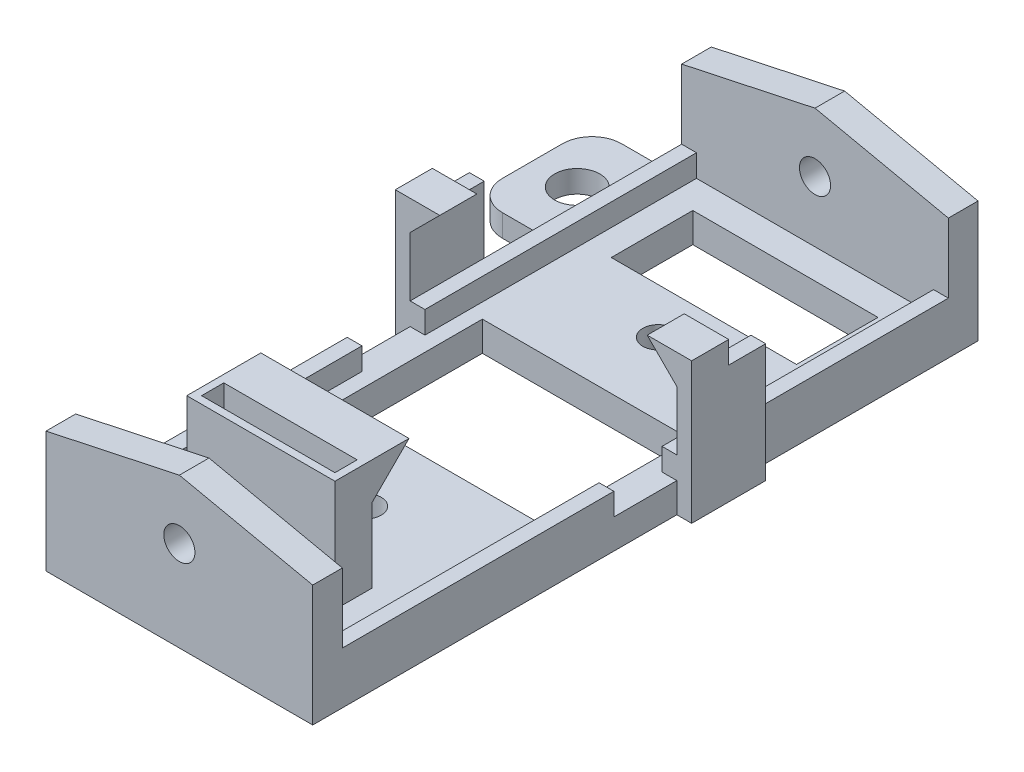
SolidWorks part; units mm, degrees
ref_plane "Front Plane" through (0, 0, 0) normal (0, 0, 1) x (1, 0, 0)
ref_plane "Top Plane" through (0, 0, 0) normal (0, 1, 0) x (1, 0, 0)
ref_plane "Right Plane" through (0, 0, 0) normal (1, 0, 0) x (0, 0, -1)
sketch "Sketch1" plane through (0, 0, 0) normal (0, 0, 1) x (1, 0, 0)
  line L2 (-40.4, 110) -> (0, 118.6383) construction
  line L3 (-18, 114.7896) -> (0, 114.7896)
  line L4 (0, 114.7896) -> (18, 114.7896)
  line L5 (0, 118.6383) -> (40.4, 110) construction
  line L11 (18, 114.7896) -> (18, 121.7896)
  line L12 (18, 121.7896) -> (16, 121.7896)
  line L13 (16, 121.7896) -> (16, 118.7896)
  line L14 (16, 118.7896) -> (-16, 118.7896)
  line L15 (-16, 118.7896) -> (-16, 121.7896)
  line L16 (-16, 121.7896) -> (-18, 121.7896)
  line L17 (-18, 121.7896) -> (-18, 114.7896)
  point P15 (0, 118.7896)
  dimension "D1" = 32
  dimension "D2" = 2
  dimension "D3" = 3
  dimension "D4" = 4
extrude "Boss-Extrude1" add sketch "Sketch1" along normal up to surface (89.8 mm away)
sketch "Sketch2" plane through (0, 114.7896, 0) normal (0, -1, 0) x (1, 0, 0)
  line L0 (18, 89.8) -> (18, 0) construction
  line L5 (-14, 54.9) -> (14, 54.9)
  line L6 (-14, 54.9) -> (-14, 34.9)
  line L7 (-14, 34.9) -> (14, 34.9)
  line L8 (14, 54.9) -> (14, 34.9)
  point P4 (0, 34.9)
  point P8 (18, 44.9)
  point P9 (14, 44.9)
  dimension "D1" = 4
  dimension "D2" = 20
extrude "Cut-Extrude1" cut sketch "Sketch2" against normal up to next
sketch "Sketch3" plane through (-18, 0, 0) normal (-1, 0, 0) x (0, 0, 1)
  line L0 (89.8, 121.7896) -> (0, 121.7896) construction
  line L1 (40.65, 118.7896) -> (49.15, 118.7896)
  line L2 (40.65, 118.7896) -> (40.65, 121.7896)
  line L3 (40.65, 121.7896) -> (49.15, 121.7896)
  line L4 (49.15, 118.7896) -> (49.15, 121.7896)
  line L5 (89.8, 118.7896) -> (0, 118.7896) construction
  point P9 (44.9, 121.7896)
  point P10 (44.9, 121.7896)
  dimension "D1" = 8.5
extrude "Cut-Extrude2" cut sketch "Sketch3" against normal through all
sketch "Sketch4" plane through (0, 118.7896, 0) normal (0, 1, 0) x (1, 0, 0)
  circle A0 centre (0, -25.15) radius 2.1 construction
  circle A1 centre (0, -64.65) radius 2.1 construction
  circle A2 centre (0, -25.15) radius 2.1
  circle A3 centre (0, -64.65) radius 2.1
extrude "Cut-Extrude3" cut sketch "Sketch4" against normal through all
ref_plane "Plane2" through (0, 0, 44.9) normal (0, 0, -1) x (-1, 0, 0)
sketch "Sketch5" plane through (0, 0, 0) normal (0, 0, 1) x (1, 0, 0)
  line L0 (-18, 114.7896) -> (-18, 131.1512)
  line L1 (-56.4, 122.9405) -> (0, 135) construction
  line L2 (-18, 131.1512) -> (0, 135)
  line L3 (0, 135) -> (18, 131.1512)
  line L4 (0, 135) -> (56.4, 122.9405) construction
  line L5 (18, 131.1512) -> (18, 114.7896)
  line L6 (18, 114.7896) -> (-18, 114.7896)
  line L7 (0.6273, 134.8659) -> (54.0273, 123.4479) construction
  line L8 (-54.0273, 123.4479) -> (-0.6273, 134.8659) construction
  circle A0 centre (0, 127) radius 2.1
  dimension "D1" = 4.2
  dimension "D2" = 8
extrude "Boss-Extrude2" add sketch "Sketch5" along normal blind 4
mirror "Mirror1" about plane through (0, 0, 44.9) normal (0, 0, -1) of "Boss-Extrude2"
sketch "Sketch6" plane through (0, 118.7896, 0) normal (0, 1, 0) x (1, 0, 0)
  line L1 (12.5, -19) -> (-12.5, -19)
  line L2 (12.5, -19) -> (12.5, -8)
  line L3 (12.5, -8) -> (-12.5, -8)
  line L4 (-12.5, -19) -> (-12.5, -8)
  point P4 (0, -8)
  dimension "D1" = 11
  dimension "D2" = 25
  dimension "D3" = 8
extrude "Cut-Extrude4" cut sketch "Sketch6" against normal through all
sketch "Sketch8" plane through (0, 118.7896, 0) normal (0, 1, 0) x (1, 0, 0)
  line L0 (16, -85.8) -> (-16, -85.8) construction
  line L1 (9, -77.8) -> (-9, -77.8)
  line L2 (9, -77.8) -> (9, -74.8)
  line L3 (9, -74.8) -> (-9, -74.8)
  line L4 (-9, -77.8) -> (-9, -74.8)
  line L6 (10, -73.8) -> (-10, -73.8)
  line L7 (-10, -78.8) -> (-10, -73.8)
  line L8 (10, -78.8) -> (-10, -78.8)
  line L9 (10, -78.8) -> (10, -73.8)
  point P6 (0, -85.8)
  point P7 (0, -77.8)
  dimension "D1" = 8
  dimension "D2" = 3
  dimension "D3" = 18
  dimension "D4" = 1
extrude "Boss-Extrude3" add sketch "Sketch8" along normal blind 15
sketch "Sketch9" plane through (-10, 0, 0) normal (-1, 0, 0) x (0, 0, 1)
  line L0 (73.8, 128.7896) -> (68.8, 133.7896)
  line L1 (73.8, 133.7896) -> (73.8, 118.7896) construction
  line L2 (68.8, 133.7896) -> (73.8, 133.7896)
  line L3 (73.8, 133.7896) -> (73.8, 128.7896)
  dimension "D1" = 5
  dimension "D2" = 45
extrude "Boss-Extrude4" add sketch "Sketch9" against normal up to surface (20 mm away) up to face at (10, 126.2896, 76.3)
sketch "Sketch13" plane through (0, 118.7896, 0) normal (0, 1, 0) x (1, 0, 0)
  line L4 (-9, -77.8) -> (9, -77.8)
  line L5 (9, -77.8) -> (9, -74.8)
  line L6 (9, -74.8) -> (-9, -74.8)
  line L7 (-9, -74.8) -> (-9, -77.8)
  line L8 (-9, -77.8) -> (9, -77.8)
  line L9 (9, -77.8) -> (9, -74.8)
  line L10 (9, -74.8) -> (-9, -74.8)
  line L11 (-9, -74.8) -> (-9, -77.8)
  dimension "D1" = 0
extrude "Cut-Extrude5" cut sketch "Sketch13" against normal through all
sketch "Sketch10" plane through (0, 114.7896, 0) normal (0, 1, 0) x (1, 0, 0)
  line L0 (18, -40.65) -> (18, -4) construction
  line L1 (18, -40.65) -> (20, -40.65)
  line L2 (18, -40.65) -> (18, -30.65)
  line L3 (18, -30.65) -> (20, -30.65)
  line L4 (20, -40.65) -> (20, -30.65)
  line L5 (0, -1000) -> (0, 49000) construction
  line L6 (-18, -30.65) -> (-20, -30.65)
  line L7 (-18, -40.65) -> (-18, -30.65)
  line L8 (-18, -40.65) -> (-20, -40.65)
  line L9 (-20, -40.65) -> (-20, -30.65)
  dimension "D1" = 10
  dimension "D2" = 2
extrude "Boss-Extrude5" add sketch "Sketch10" along normal offset from surface (16 mm away) 3
sketch "Sketch12" plane through (0, 0, 40.65) normal (0, 0, 1) x (1, 0, 0)
  line L0 (20, 129.7896) -> (20, 133.7896)
  line L1 (20, 133.7896) -> (14, 133.7896)
  line L2 (14, 133.7896) -> (18, 129.7896)
  line L3 (18, 129.7896) -> (20, 129.7896)
  line L4 (-18, 133.7896) -> (18, 133.7896) construction
  line L5 (18, 114.7896) -> (18, 131.1512) construction
  line L6 (20, 130.7896) -> (20, 114.7896) construction
  line L7 (18, 130.7896) -> (18, 121.7896) construction
  line L8 (0, -868.0678) -> (0, 49131.9322) construction
  line L9 (-18, 129.7896) -> (-20, 129.7896)
  line L10 (-14, 133.7896) -> (-18, 129.7896)
  line L11 (-20, 133.7896) -> (-14, 133.7896)
  line L12 (-20, 129.7896) -> (-20, 133.7896)
  dimension "D1" = 45
  dimension "D2" = 6
extrude "Boss-Extrude6" add sketch "Sketch12" against normal blind 5
sketch "Sketch14" plane through (0, 114.7896, 0) normal (0, 1, 0) x (1, 0, 0)
  line L0 (-18, -30.65) -> (-18, -4) construction
  line L1 (-18, -4) -> (-30.1, -4)
  line L2 (-18, -4) -> (-18, -20.1)
  line L3 (-18, -20.1) -> (-30.1, -20.1)
  line L4 (-30.1, -4) -> (-30.1, -20.1)
  circle A0 centre (-24.05, -12.05) radius 3.05
  point P9 (-30.1, -12.05)
  point P10 (-24.05, -20.1)
  dimension "D1" = 6.1
  dimension "D2" = 3
  dimension "D3" = 5
extrude "Boss-Extrude7" add sketch "Sketch14" along normal blind 3
fillet "Fillet1" radius 4 2 edges at (-30.1, 116.2896, 4) (-30.1, 116.2896, 20.1)
chamfer "Chamfer1" distance 3 angle 45 2 edges at (-18, 116.2896, 20.1) (-18, 116.2896, 4)
equation "\"width\"= 24"
equation "\"thk\"= 3"
equation "\"holesize\"= 4.2"
equation "\"holedistance\"= ( 20 + 12 ) / 2"
equation "\"threaded_hole\"= 3.9"
equation "\"fillet_radius\"= 2"
equation "\"ground_clearance\"= 25"
equation "\"tire_thk\"= 3"
equation "\"innerwheel_diam\" = \"wheel_diam\"-2*\"tire_thk\""
equation "\"innerwheel_thk\"= 8"
equation "\"wheel_diam\"= 2*(\"width\"/2+\"ground_clearance\")"
equation "\"coloursensor_holesize\"= 2.65"
equation "\"hole_to_edge\" = 4"
equation "\"D1@Sketch5\"=\"holesize\""
